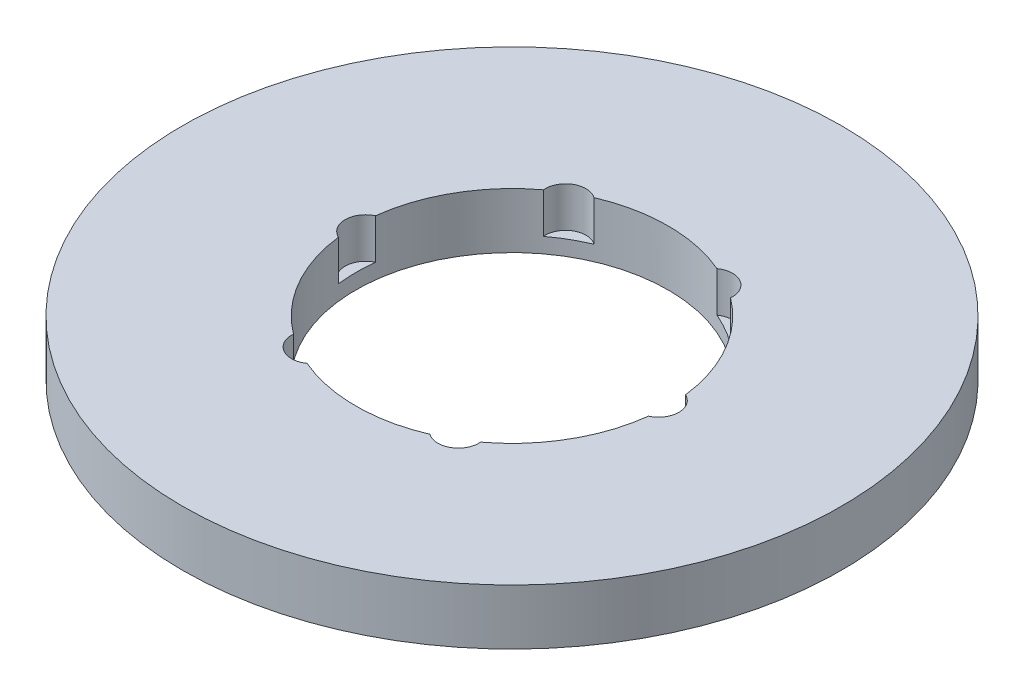
SolidWorks part; units mm, degrees
ref_plane "Front Plane" through (0, 0, 0) normal (0, 0, 1) x (1, 0, 0)
ref_plane "Top Plane" through (0, 0, 0) normal (0, 1, 0) x (1, 0, 0)
ref_plane "Right Plane" through (0, 0, 0) normal (1, 0, 0) x (0, 0, -1)
sketch "Sketch1" plane through (0, 0, 0) normal (0, 1, 0) x (1, 0, 0)
  circle A0 centre (0, 0) radius 95
  dimension "FLANGE_OD" = 190
extrude "Boss-Extrude1" add sketch "Sketch1" along normal blind 16
sketch "Sketch2" plane through (0, 0, 0) normal (0, 1, 0) x (1, 0, 0)
  circle A0 centre (0, 0) radius 45
  dimension "BORE_D" = 90
extrude "Cut-Extrude1" cut sketch "Sketch2" along normal through all
sketch "Sketch3" plane through (0, 16, 0) normal (0, 1, 0) x (1, 0, 0)
  circle A0 centre (0, 0) radius 42.2255 construction
  circle A1 centre (-42.2255, 0) radius 5.88
  dimension "BOLT_D" = 11.76
  dimension "BOLT_PCD" = 84.451
extrude "Cut-Extrude2" cut sketch "Sketch3" against normal blind 11.623
pattern_circular "CirPattern1" count 6 over 360 about axis through (0, 0, 0) along (0, 1, 0) of "Cut-Extrude2"
